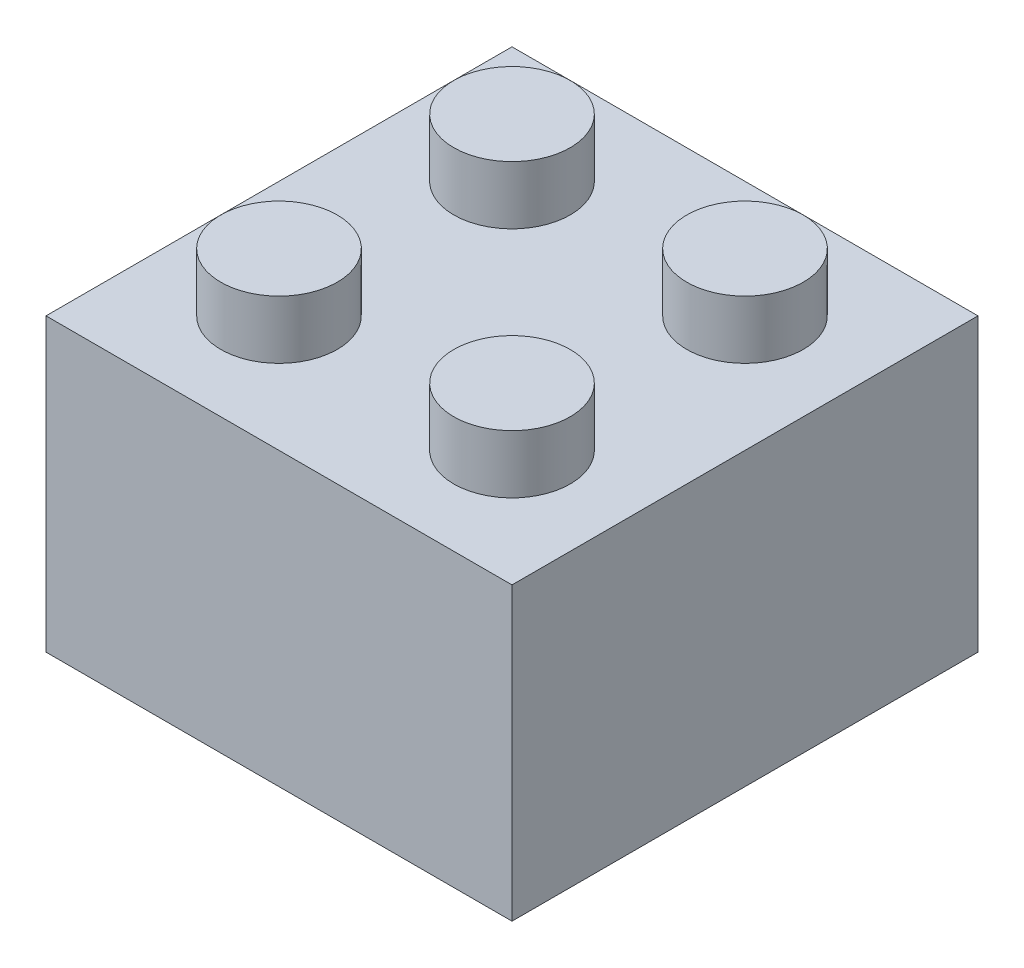
SolidWorks part; units mm, degrees
ref_plane "Front Plane" through (0, 0, 0) normal (0, 0, 1) x (1, 0, 0)
ref_plane "Top Plane" through (0, 0, 0) normal (0, 1, 0) x (1, 0, 0)
ref_plane "Right Plane" through (0, 0, 0) normal (1, 0, 0) x (0, 0, -1)
sketch "Sketch1" plane through (0, 0, 0) normal (0, 1, 0) x (1, 0, 0)
  line L1 (8, -8) -> (-8, -8)
  line L2 (8, -8) -> (8, 8)
  line L3 (8, 8) -> (-8, 8)
  line L4 (-8, -8) -> (-8, 8)
  line L5 (8, -8) -> (-8, 8) construction
  line L6 (8, 8) -> (-8, -8) construction
  point P0 (0, 0)
  dimension "D1" = 16
  dimension "D2" = 16
extrude "Boss-Extrude1" add sketch "Sketch1" along normal blind 10
sketch "Sketch2" plane through (0, 10, 0) normal (0, 1, 0) x (1, 0, 0)
  line L0 (0, 7.6616) -> (0, 0) construction
  line L1 (0, 0) -> (7.8224, 0) construction
  line L2 (-8, 8) -> (-8, -8) construction
  line L3 (8, 8) -> (-8, 8) construction
  circle A0 centre (-4, 4) radius 2
  circle A1 centre (4, 4) radius 2
  circle A2 centre (4, -4) radius 2
  circle A3 centre (-4, -4) radius 2
  dimension "D1" = 4
  dimension "D2" = 4
  dimension "D3" = 4
extrude "Boss-Extrude2" add sketch "Sketch2" along normal blind 2
shell "Shell2" thickness 1 removed face at (0, 0, 0)
sketch "Sketch3" plane through (0, 9, 0) normal (0, -1, 0) x (1, 0, 0)
  circle A0 centre (0, 0) radius 2.7
  circle A1 centre (0, 0) radius 1.7
  dimension "D1" = 3.4
  dimension "D2" = 5.4
extrude "Boss-Extrude3" add sketch "Sketch3" along normal blind 9
